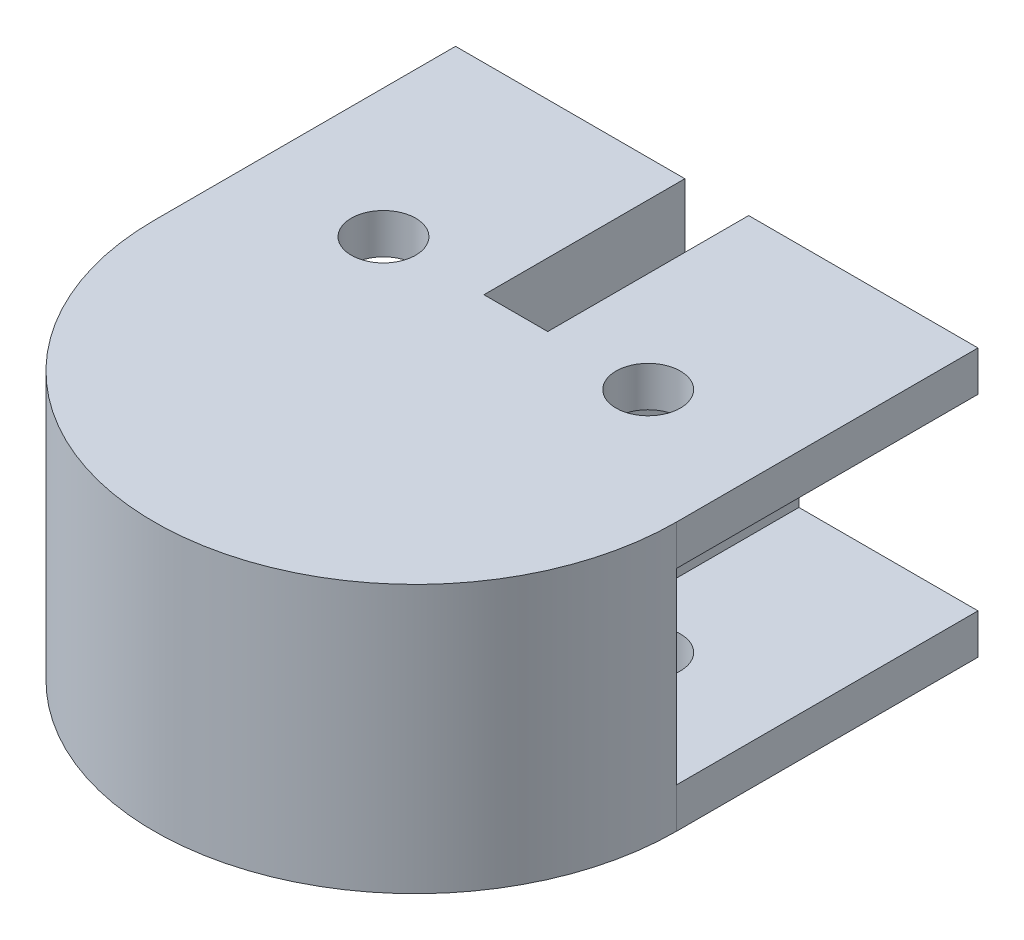
SolidWorks part; units mm, degrees
ref_plane "Front Plane" through (0, 0, 0) normal (0, 0, 1) x (1, 0, 0)
ref_plane "Top Plane" through (0, 0, 0) normal (0, 1, 0) x (1, 0, 0)
ref_plane "Right Plane" through (0, 0, 0) normal (1, 0, 0) x (0, 0, -1)
sketch "Sketch1" plane through (0, 0, 0) normal (0, 1, 0) x (1, 0, 0)
  line L0 (-1.5875, 0) -> (1.5875, 0)
  line L1 (1.5875, 0) -> (1.5875, 10)
  line L2 (1.5875, 10) -> (13, 10)
  line L3 (13, 10) -> (13, -5)
  line L4 (0, 0) -> (0, -18) construction
  line L5 (-13, 10) -> (-13, -5)
  line L6 (-1.5875, 10) -> (-13, 10)
  line L7 (-1.5875, 0) -> (-1.5875, 10)
  arc A0 (-13, -5) -> (13, -5) centre (0, -5) ccw
  circle A1 centre (6.5875, 0) radius 1.6
  circle A2 centre (-6.5875, 0) radius 1.6
  point P10 (0, 0)
  dimension "D5" = 3.2
  dimension "D1" = 1.5875
  dimension "D2" = 11.4125
  dimension "D3" = 15
  dimension "D4" = 10
  dimension "D6" = 5
extrude "Boss-Extrude1" add sketch "Sketch1" along normal blind 2
sketch "Sketch3" plane through (0, 0, 0) normal (0, -1, 0) x (1, 0, 0)
  line L0 (4.0875, -10) -> (1.5875, -10)
  line L1 (13, -10) -> (1.5875, -10) construction
  line L2 (1.5875, -10) -> (1.5875, 0)
  line L3 (1.5875, 0) -> (-1.5875, 0)
  line L4 (-1.5875, 0) -> (-1.5875, -10)
  line L5 (-1.5875, -10) -> (-4.0875, -10)
  line L6 (-1.5875, -10) -> (-13, -10) construction
  line L7 (-4.0875, -10) -> (-4.0875, 5)
  line L8 (-4.0875, 5) -> (-13, 5)
  line L9 (4.0875, -10) -> (4.0875, 5)
  line L10 (4.0875, 5) -> (13, 5)
  arc A0 (13, 5) -> (-13, 5) centre (0, 5) ccw
  dimension "D1" = 2.5
extrude "Boss-Extrude3" add sketch "Sketch3" along normal blind 4.665
ref_plane "Plane2" through (0, -4.665, 0) normal (0, -1, 0) x (-1, 0, 0)
mirror "Mirror11" about plane through (0, -4.665, 0) normal (0, -1, 0) of "Boss-Extrude3"
mirror "Mirror12" about plane through (0, -4.665, 0) normal (0, -1, 0) of "Boss-Extrude1"
